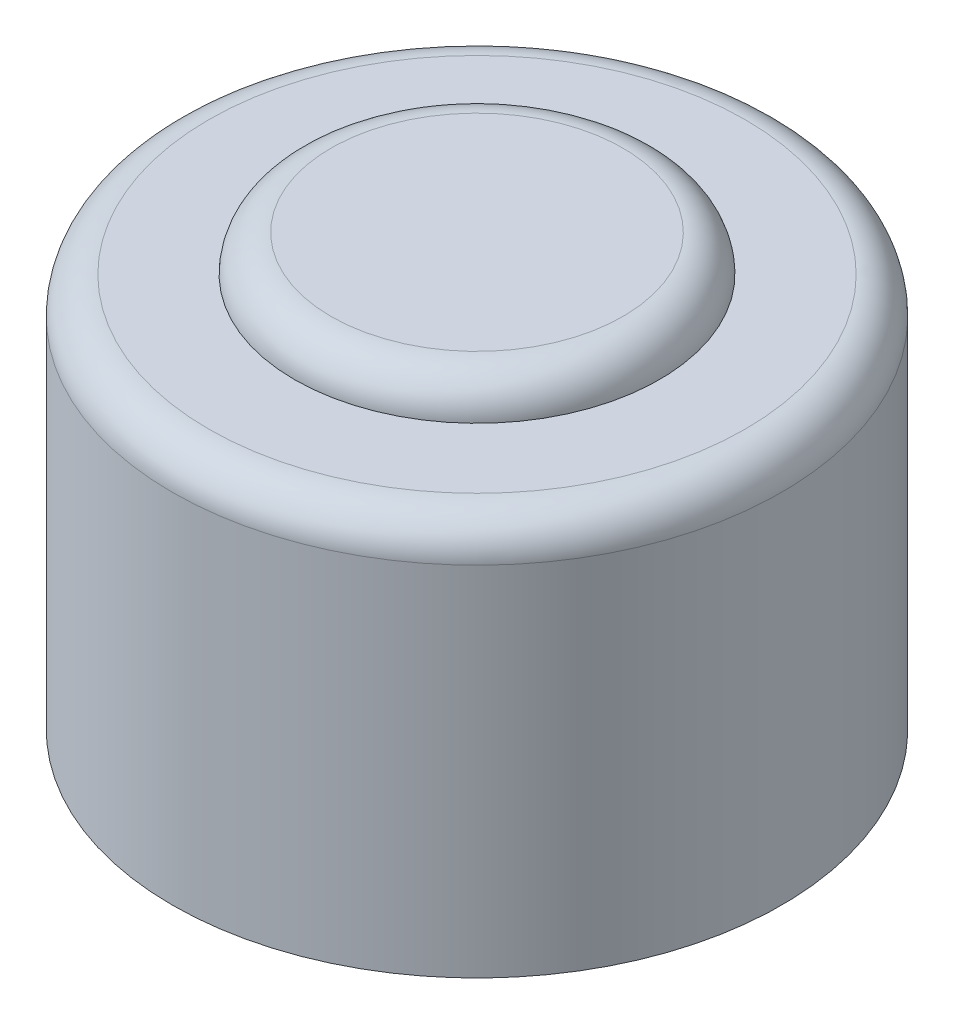
SolidWorks part; units mm, degrees
ref_plane "Front Plane" through (0, 0, 0) normal (0, 0, 1) x (1, 0, 0)
ref_plane "Top Plane" through (0, 0, 0) normal (0, 1, 0) x (1, 0, 0)
ref_plane "Right Plane" through (0, 0, 0) normal (1, 0, 0) x (0, 0, -1)
sketch "Sketch1" plane through (0, 0, 0) normal (0, 1, 0) x (1, 0, 0)
  circle A0 centre (0, 0) radius 19.05
  dimension "D1" = 38.1
extrude "Boss-Extrude1" add sketch "Sketch1" along normal blind 1.27
sketch "Sketch2" plane through (0, 1.27, 0) normal (0, 1, 0) x (1, 0, 0)
  circle A0 centre (0, 0) radius 21.209
  dimension "D1" = 42.418
extrude "Boss-Extrude2" add sketch "Sketch2" along normal blind 27.432
sketch "Sketch3" plane through (0, 28.702, 0) normal (0, 1, 0) x (1, 0, 0)
  circle A0 centre (0, 0) radius 12.7
  dimension "D1" = 25.4
extrude "Boss-Extrude3" add sketch "Sketch3" along normal blind 2.54
fillet "Fillet2" radius 2.54 2 edges at (0, 28.702, 21.209) (0, 31.242, 12.7)
